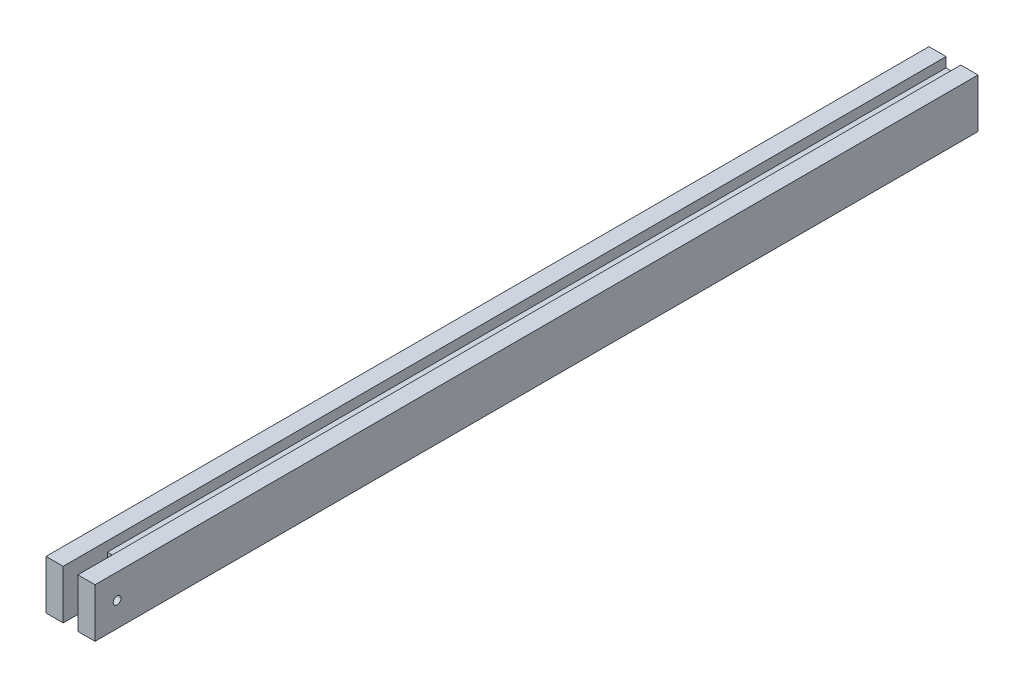
SolidWorks part; units mm, degrees
ref_plane "Front" through (0, 0, 0) normal (0, 0, 1) x (1, 0, 0)
ref_plane "Top" through (0, 0, 0) normal (0, 1, 0) x (1, 0, 0)
ref_plane "Right" through (0, 0, 0) normal (1, 0, 0) x (0, 0, -1)
sketch "Esquisse1" plane through (0, 0, 0) normal (0, 0, 1) x (1, 0, 0)
  line L1 (0, 0) -> (100, 0)
  line L2 (0, 0) -> (0, 100)
  line L3 (0, 100) -> (100, 100)
  line L4 (100, 0) -> (100, 100)
  dimension "D1" = 100
  dimension "D2" = 100
extrude "Boss.-Extru.1" add sketch "Esquisse1" along normal blind 1800
sketch "Esquisse2" plane through (0, 0, 0) normal (0, -1, 0) x (1, 0, 0)
  line L0 (0, 1800) -> (100, 1800) construction
  line L1 (35, 1800) -> (65, 1800)
  line L2 (35, 1800) -> (35, 1710)
  line L3 (35, 1710) -> (65, 1710)
  line L4 (65, 1800) -> (65, 1710)
  line L5 (50, 1710) -> (50, 1800) construction
  dimension "D1" = 30
  dimension "D2" = 90
extrude "Enlèv. mat.-Extru.1" cut sketch "Esquisse2" against normal through all
sketch "Esquisse3" plane through (100, 0, 0) normal (1, 0, 0) x (0, 0, -1)
  line L0 (-1800, 50) -> (-1755, 50) construction
  line L1 (-1800, 0) -> (-1800, 100) construction
  line L2 (-1755, 50) -> (-1710, 50) construction
  line L3 (-1710, 100) -> (-1710, 0) construction
  circle A0 centre (-1755, 50) radius 8
  dimension "D1" = 16
extrude "Enlèv. mat.-Extru.2" cut sketch "Esquisse3" against normal through all
sketch "Esquisse4" plane through (0, 0, 0) normal (0, 0, -1) x (-1, 0, 0)
  line L0 (0, 50) -> (-100, 50) construction
  line L4 (0, 100) -> (0, 0) construction
  line L5 (-100, 0) -> (-100, 100) construction
  line L6 (-100, 100) -> (0, 100) construction
  line L7 (-65, 100) -> (-35, 100)
  line L8 (-65, 100) -> (-65, 80)
  line L9 (-65, 80) -> (-35, 80)
  line L10 (-35, 100) -> (-35, 80)
  line L11 (-50, 80) -> (-50, 50) construction
  line L12 (-35, 0) -> (-35, 20)
  line L13 (-65, 20) -> (-35, 20)
  line L14 (-65, 0) -> (-65, 20)
  line L15 (-65, 0) -> (-35, 0)
  dimension "D1" = 20
  dimension "D2" = 30
extrude "Enlèv. mat.-Extru.3" cut sketch "Esquisse4" against normal through all
